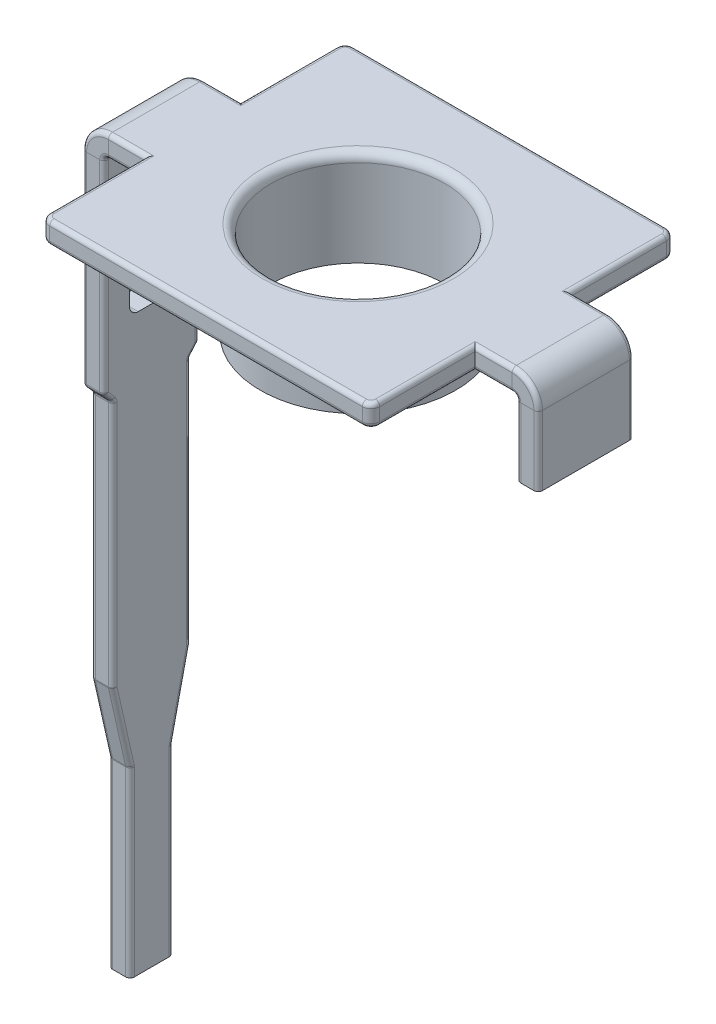
SolidWorks part; units mm, degrees
ref_plane "Front Plane" through (0, 0, 0) normal (0, 0, 1) x (1, 0, 0)
ref_plane "Top Plane" through (0, 0, 0) normal (0, 1, 0) x (1, 0, 0)
ref_plane "Right Plane" through (0, 0, 0) normal (1, 0, 0) x (0, 0, -1)
sketch "Sketch1" plane through (0, 0, 0) normal (0, 1, 0) x (1, 0, 0)
  line L1 (-3.8, 3.5) -> (3.8, 3.5)
  line L2 (-3.8, 3.5) -> (-3.8, -3.5)
  line L3 (-3.8, -3.5) -> (3.8, -3.5)
  line L4 (3.8, 3.5) -> (3.8, -3.5)
  line L5 (-3.8, 3.5) -> (3.8, -3.5) construction
  line L6 (-3.8, -3.5) -> (3.8, 3.5) construction
  point P0 (0, 0)
  dimension "D1" = 7
  dimension "D2" = 7.6
extrude "Boss-Extrude1" add sketch "Sketch1" along normal blind 2.2
sketch "Sketch2" plane through (0, 2.2, 0) normal (0, 1, 0) x (1, 0, 0)
  circle A0 centre (0, 0) radius 2
  dimension "D1" = 4
extrude "Cut-Extrude1" cut sketch "Sketch2" against normal through all
fillet "Fillet1" radius 0.2 1 edges at (0, 2.2, 2)
sketch "Sketch3" plane through (0, 0, 0) normal (0, -1, 0) x (1, 0, 0)
  line L1 (-3.8, 3.5) -> (3.8, 3.5)
  line L2 (-3.8, 3.5) -> (-3.8, -3.5)
  line L3 (-3.8, -3.5) -> (3.8, -3.5)
  line L4 (3.8, 3.5) -> (3.8, -3.5)
  line L5 (-3.8, 3.5) -> (3.8, -3.5) construction
  line L6 (-3.8, -3.5) -> (3.8, 3.5) construction
  circle A0 centre (0, 0) radius 2.25
extrude "Cut-Extrude2" cut sketch "Sketch3" against normal offset from surface (1.7 mm away) 0.5 up to face at (0, 2.2, 2.2)
sketch "Sketch4" plane through (-3.8, 0, 0) normal (-1, 0, 0) x (0, 0, 1)
  line L1 (3.5, 2.2) -> (3.5, 1.7) construction
  line L16 (-1.1, 2.2) -> (1.1, 2.2)
  line L17 (-1.1, 2.2) -> (-1.1, 1.7)
  line L18 (-1.1, 1.7) -> (1.1, 1.7)
  line L19 (1.1, 2.2) -> (1.1, 1.7)
  line L20 (-1.1, 2.2) -> (1.1, 1.7) construction
  line L21 (-1.1, 1.7) -> (1.1, 2.2) construction
  point P0 (0, 1.95)
  point P2 (0, 1.95)
  dimension "D1" = 2.2
  dimension "D2" = 3.5
  dimension "D3" = 0.5
sketch "Sketch6" plane through (0, 0, 0) normal (0, 0, 1) x (1, 0, 0)
  line L0 (-3.8, 1.95) -> (-4.65, 1.95)
  line L1 (-5, 1.6) -> (-5, 0)
  arc A0 (-4.65, 1.95) -> (-5, 1.6) centre (-4.65, 1.6) ccw
  dimension "D1" = 0.35
  dimension "D2" = 5
sweep "Sweep12" add profiles "Sketch4" path "Sketch6"
mirror "Mirror1" about plane through (0, 0, 0) normal (1, 0, 0) of "Sweep12"
sketch "Sketch8" plane through (0, 0, 0) normal (0, -1, 0) x (1, 0, 0)
  line L1 (-5.25, 1.1) -> (-4.75, 1.1)
  line L2 (-5.25, 1.1) -> (-5.25, -1.1)
  line L3 (-5.25, -1.1) -> (-4.75, -1.1)
  line L4 (-4.75, 1.1) -> (-4.75, -1.1)
extrude "Boss-Extrude2" add sketch "Sketch8" along normal blind 15
sketch "Sketch9" plane through (0, 0, 0) normal (1, 0, 0) x (0, 0, -1)
  line L0 (0, -16.1319) -> (0, 4.9512) construction
  line L1 (-0.5, -15) -> (0.5, -15)
  line L2 (1.1, -15) -> (-1.1, -15) construction
  line L3 (0.5, -15) -> (0.5, -10.8)
  line L5 (0.9, -9.0236) -> (0.9, -3.3)
  line L7 (1.9641, -3.3) -> (1.9641, -15.974)
  line L8 (1.9641, -15.974) -> (-1.9641, -15.974)
  line L9 (-1.9641, -3.3) -> (-1.9641, -15.974)
  line L11 (-0.9, -9.0236) -> (-0.9, -3.3)
  line L13 (-0.5, -15) -> (-0.5, -10.8)
  line L15 (0.5, -10.8) -> (0.9, -9.0236)
  line L16 (-0.5, -10.8) -> (-0.9, -9.0236)
  line L17 (0.9, -3.3) -> (1.9641, -2.0808)
  line L18 (1.9641, -2.0808) -> (1.9641, -3.3)
  line L19 (-1.9641, -3.3) -> (-1.9641, -2.0808)
  line L20 (-1.9641, -2.0808) -> (-0.9, -3.3)
  point P14 (0, -15.974)
  point P19 (0, -15)
  dimension "D1" = 0.5
  dimension "D2" = 0.9
extrude "Cut-Extrude3" cut sketch "Sketch9" against normal through all
sketch "Sketch10" plane through (-5.25, 0, 0) normal (-1, 0, 0) x (0, 0, 1)
  line L1 (-0.2895, 0.7262) -> (0.3105, 0.7262)
  line L2 (-0.4895, 0.5262) -> (-0.4895, -1.5738)
  line L3 (-0.2895, -1.7738) -> (0.3105, -1.7738)
  line L4 (0.5105, 0.5262) -> (0.5105, -1.5738)
  line L5 (-0.4895, 0.7262) -> (0.5105, -1.7738) construction
  line L6 (-0.4895, -1.7738) -> (0.5105, 0.7262) construction
  arc A0 (-0.4895, -1.5738) -> (-0.2895, -1.7738) centre (-0.2895, -1.5738) ccw
  arc A1 (0.3105, -1.7738) -> (0.5105, -1.5738) centre (0.3105, -1.5738) ccw
  arc A2 (0.3105, 0.7262) -> (0.5105, 0.5262) centre (0.3105, 0.5262) cw
  arc A3 (-0.2895, 0.7262) -> (-0.4895, 0.5262) centre (-0.2895, 0.5262) ccw
  point P0 (0.0105, -0.5238)
  dimension "D3" = 0.2
  dimension "D1" = 2.5
  dimension "D2" = 1
extrude "Cut-Extrude4" cut sketch "Sketch10" against normal up to surface (0.5 mm away) up to face at (-4.75, -6.5991, 0)
fillet "Fillet2" radius 0.2 4 edges at (3.8, 1.95, 3.5) (-3.8, 1.95, 3.5) (-3.8, 1.95, -3.5) (3.8, 1.95, -3.5)
fillet "Fillet3" radius 0.1 44 edges at (3.8, 1.7, 2.2) (3.7414, 1.7, 3.4414) (-3.8, 1.7, 2.2) (-3.7414, 1.7, 3.4414) (3.8, 1.7, -2.2) (3.7414, 1.7, -3.4414) (0, 1.7, -3.5) (-3.7414, 1.7, -3.4414) (-4.225, 1.7, -1.1) (-4.7207, 1.6707, -1.1) (-4.225, 2.2, -1.1) (-5.0743, 2.0243, -1.1) (-4.225, 1.7, 1.1) (-4.7207, 1.6707, 1.1) (-4.225, 2.2, 1.1) (-5.25, -0.7354, 1.1) (4.225, 1.7, 1.1) (4.7207, 1.6707, 1.1) (4.75, 0.8, -1.1) (4.7207, 1.6707, -1.1) (5.25, 0.8, 1.1) (5.0743, 2.0243, 1.1) (5.25, 0.8, -1.1) (5.0743, 2.0243, -1.1) (-3.8, 2.2, 2.2) (-3.7414, 2.2, 3.4414) (3.8, 2.2, 2.2) (3.7414, 2.2, 3.4414) (3.8, 2.2, -2.2) (3.7414, 2.2, -3.4414) (-3.8, 2.2, -2.2) (-3.7414, 2.2, -3.4414) (0, 1.7, 3.5) (-3.8, 1.7, -2.2) (-4.75, -0.7354, -1.1) (-5.25, -0.7354, -1.1) (-4.75, -0.7354, 1.1) (-5.0743, 2.0243, 1.1) (4.75, 0.8, 1.1) (4.225, 1.7, -1.1) (4.225, 2.2, 1.1) (4.225, 2.2, -1.1) (0, 2.2, 3.5) (0, 2.2, -3.5)
fillet "Fillet4" radius 0.1 28 edges at (-5, -3.0709, -1.1) (-5, -3.0709, 1.1) (-5.2207, -3.1044, -1.0707) (-4.7793, -3.1044, -1.0707) (-5.2207, -3.1044, 1.0707) (-4.7793, -3.1044, 1.0707) (-5.25, -12.9, 0.5) (-4.75, -12.9, 0.5) (-5.25, -12.9, -0.5) (-4.75, -12.9, -0.5) (-5.25, -3.2427, -0.95) (-4.75, -3.2427, -0.95) (-5.25, -3.2427, 0.95) (-4.75, -3.2427, 0.95) (-5, -10.8, 0.5) (-5.25, -9.9118, 0.7) (-4.75, -9.9118, 0.7) (-5.25, -9.9118, -0.7) (-5, -10.8, -0.5) (-4.75, -9.9118, -0.7) (-5, -3.3, -0.9) (-5.25, -6.1618, -0.9) (-5, -9.0236, -0.9) (-4.75, -6.1618, -0.9) (-5, -9.0236, 0.9) (-5.25, -6.1618, 0.9) (-5, -3.3, 0.9) (-4.75, -6.1618, 0.9)
